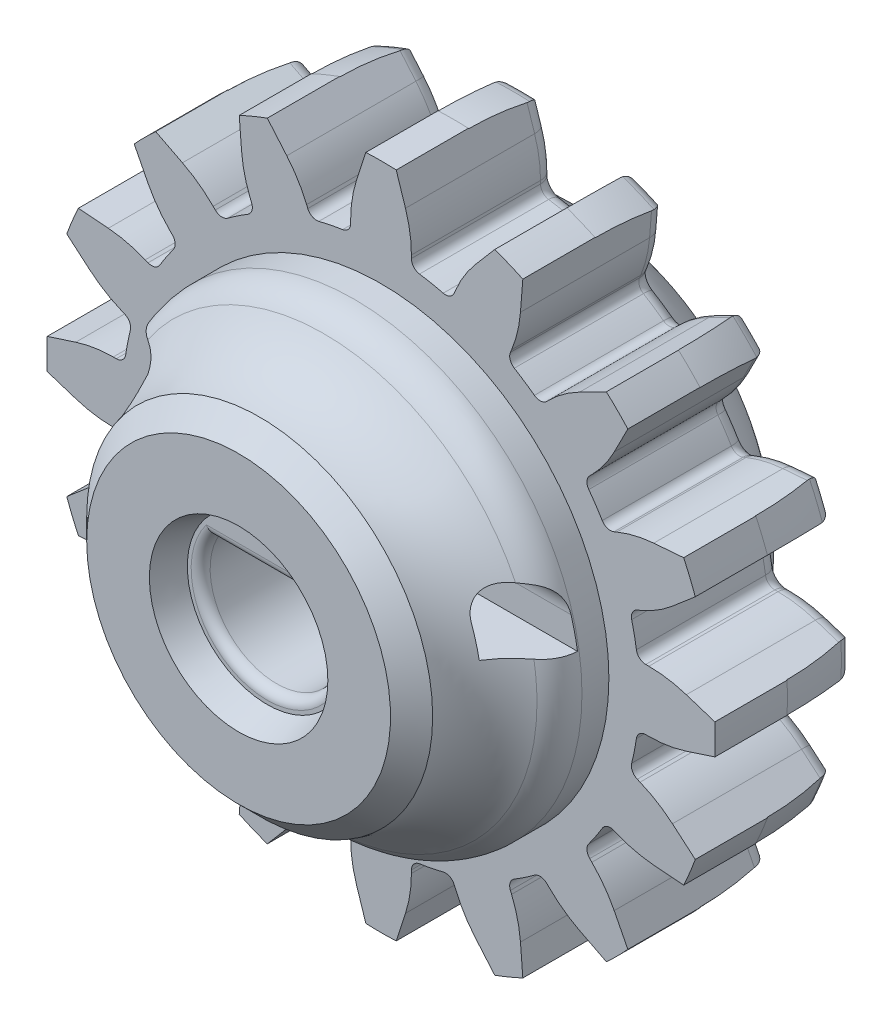
SolidWorks part; units mm, degrees
ref_plane "Front Plane" through (0, 0, 0) normal (0, 0, 1) x (1, 0, 0)
ref_plane "Top Plane" through (0, 0, 0) normal (0, 1, 0) x (1, 0, 0)
ref_plane "Right Plane" through (0, 0, 0) normal (1, 0, 0) x (0, 0, -1)
ref_axis "Axis1" through (0, 0, -12.1515) along (0, 0, 1)
sketch "Sketch1" plane through (0, 0, 0) normal (0, 0, 1) x (1, 0, 0)
  line L0 (0, 0) -> (6.8, 0)
  line L1 (0, 0) -> (0, 6.8) construction
  line L17 (0, 0) -> (0, 6.8)
  arc A0 (6.8, 0) -> (0, 6.8) centre (0, 0) ccw
  dimension "D1" = 13.6
sketch "Sketch4" plane through (0, 0, 0) normal (0, 0, 1) x (1, 0, 0)
  line L0 (0, 0) -> (0, 8.8) construction
  line L1 (-0.4, 8.7909) -> (-0.8, 7.5578)
  line L2 (-0.8, 7.5578) -> (-0.8, 6.7528)
  line L3 (0.8, 7.5578) -> (0.8, 6.7528)
  line L4 (0.4, 8.7909) -> (0.8, 7.5578)
  arc A0 (0.4, 8.7909) -> (-0.4, 8.7909) centre (0, 0) ccw
  arc A2 (0.8, 6.7528) -> (-0.8, 6.7528) centre (0, 0) ccw
  circle A3 centre (0, 0) radius 7.6 construction
  dimension "D1" = 0.4
  dimension "D3" = 15.2
  dimension "D4" = 17.6
  dimension "D2" = 0.8
sketch "Sketch5" plane through (0, 0, 0) normal (1, 0, 0) x (0, 0, -1)
  line L0 (-3, 0) -> (0, 0)
  line L1 (-3.75, 2.1) -> (-3.75, 4.5)
  line L2 (0, 6) -> (3.1175, 6) construction
  line L3 (-2, 0) -> (-2, 5.105) construction
  line L4 (-1.25, 0) -> (-1.25, 6) construction
  line L5 (0, 0) -> (0, 6)
  line L6 (-3.75, 4.5) -> (-6.015, 4.5) construction
  line L7 (0, 6) -> (-1.25, 6)
  line L8 (-3, 0) -> (-3, 2.1)
  line L9 (-3, 2.1) -> (-3.75, 2.1)
  arc A0 (-3.75, 4.5) -> (-1.25, 6) centre (-3.75, 7.3333) ccw
  dimension "D1" = 0.75
  dimension "D2" = 4.5
  dimension "D3" = 1.75
  dimension "D4" = 2
  dimension "D5" = 6
  dimension "D6" = 2.5
  dimension "D7" = 2.1
sketch "Sketch6" plane through (0, 0, 0) normal (0, 0, 1) x (1, 0, 0)
  line L0 (1.4422, 0.9) -> (-1.4422, 0.9) construction
  line L1 (0, 0.9) -> (0, -1.7) construction
  line L2 (1.4697, 0.95) -> (-1.4697, 0.95)
  arc A1 (-1.4422, 0.9) -> (1.4422, 0.9) centre (0, 0) ccw construction
  arc A2 (-1.4697, 0.95) -> (1.4697, 0.95) centre (0, 0) ccw
  dimension "D1" = 1.7
  dimension "D2" = 2.6
  dimension "D3" = 0.05
sketch "Sketch7" plane through (0, 0, 0) normal (1, 0, 0) x (0, 0, -1)
  line L0 (-6.4219, 0.95) -> (11.2671, 0.95) construction
  line L3 (-0.75, 1.7) -> (-0.75, 0.95)
  line L4 (-0.75, 0.95) -> (-2.25, 0.95)
  line L5 (-2.25, 0.95) -> (-2.25, 1.7)
  arc A0 (-0.75, 1.7) -> (-2.25, 1.7) centre (-1.5, 1.7) ccw
  circle A1 centre (-1.5, 1.7) radius 1.4 construction
  dimension "D1" = 1.5
  dimension "D3" = 2.8
extrude "Boss-Extrude1" add sketch "Sketch1" against normal blind 3.8
mirror "Mirror1" about plane through (0, 0, 0) normal (0, 1, 0) of bodies 102
mirror "Mirror2" about plane through (0, 0, 0) normal (1, 0, 0) of bodies 104
extrude "Boss-Extrude2" add sketch "Sketch4" against normal blind 3.8
fillet "Fillet1" radius 3.2 2 edges at (-0.8, 7.5578, -1.9) (0.8, 7.5578, -1.9)
fillet "Fillet2" radius 0.25 2 edges at (0.8, 6.7528, -1.9) (-0.8, 6.7528, -1.9)
pattern_circular "CirPattern1" count 16 over 360 about axis through (0, 0, -12.1515) along (0, 0, 1) of "Fillet1", "Boss-Extrude2", "Fillet2"
sketch "Sketch3" plane through (0, 0, 0) normal (0, 0, 1) x (1, 0, 0)
  line L0 (1.375, 3.1505) -> (3.1505, 1.375)
  line L1 (3.1505, 1.375) -> (5.4544, 1.375)
  line L3 (1.375, 5.4544) -> (1.375, 3.1505)
  arc A0 (1.375, 5.4544) -> (5.4544, 1.375) centre (0, 0) cw
  dimension "D1" = 5.625
revolve "Revolve1" add sketch "Sketch5" angle 360 about axis through (0, 0, -12.1515) along (0, 0, 1) reverse direction yes
sketch "Sketch11" plane through (0, 0, 0) normal (1, 0, 0) x (0, 0, -1)
  line L0 (0, 0) -> (6.05, 0)
  line L1 (12.1515, 0) -> (-7.3064, 0) construction
  line L2 (6.05, 0) -> (6.05, 3)
  line L3 (3.8, 6) -> (3.8, 0) construction
  line L4 (3.8, 6) -> (0, 0)
  line L5 (3.8, 5.9333) -> (3.8, 6.499) construction
  line L6 (3.8, 4.4207) -> (3.8, 5.2292) construction
  arc A0 (3.8, 6) -> (6.05, 3) centre (2.925, 3) cw
  dimension "D1" = 3
  dimension "D2" = 2.25
  dimension "D3" = 6
revolve "Revolve2" add sketch "Sketch11" angle 360 about axis through (0, 0, -12.1515) along (0, 0, 1)
fillet "Fillet3" radius 1 1 edges at (6, 0, 1.25)
extrude "Cut-Extrude1" cut sketch "Sketch6" against normal through all both and the other way through all
fillet "Fillet4" radius 0.25 2 edges at (0, -1.75, 3) (0, 0.95, 3)
extrude "Cut-Extrude2" cut sketch "Sketch7" against normal through all both and the other way through all
sketch "Sketch9" plane through (0, 0, 0) normal (1, 0, 0) x (0, 0, -1)
  circle A0 centre (-1.5, 1.7) radius 0.75 construction
  circle A2 centre (-1.5, 1.7) radius 1.45
  dimension "D1" = 2.9
extrude "Cut-Extrude3" cut sketch "Sketch9" against normal through all from offset 4 offset against normal yes
sketch "Sketch12" plane through (0, 0, 0) normal (1, 0, 0) x (0, 0, -1)
  line L0 (3.8, 8.7909) -> (0, 8.7909) construction
  line L1 (1.9, 8.7909) -> (1.9, 11.1399)
  line L2 (1.9, 11.1399) -> (10.6909, 11.1399)
  line L3 (10.6909, 11.1399) -> (10.6909, 3.6716)
  line L4 (12.1515, 0) -> (-7.3064, 0) construction
  line L5 (9.8576, 3.7359) -> (10.6909, 3.6716)
  arc A0 (1.9, 8.7909) -> (9.8576, 3.7359) centre (1.9, 0) cw
revolve "Cut-Revolve1" cut sketch "Sketch12" angle 360 about axis through (0, 0, -12.1515) along (0, 0, 1)
chamfer "Chamfer2" distance 0.25 distance2 0.75 1 edges at (2.1, 0, 3.75) first distance on face at (2.1, 0, 3.75)
chamfer "Chamfer3" distance 0.5 angle 45 1 edges at (4.5, 0, 3.75)
fillet "Fillet5" radius 0.4 161 edges at (7.2679, -2.187, -3.8) (6.784, -1.9441, -3.8) (6.6193, -1.8104, -3.8) (6.6693, -1.3266, -3.8) (6.8083, -0.8605, -3.8) (7.0116, -0.8, -3.8) (7.5516, -0.7607, -3.8) (8.3046, -0.5577, -3.8) (8.5831, 0, -3.8) (8.3046, 0.5577, -3.8) (7.5516, 0.7607, -3.8) (7.0116, 0.8, -3.8) (6.8083, 0.8605, -3.8) (6.6693, 1.3266, -3.8) (6.6193, 1.8104, -3.8) (6.784, 1.9441, -3.8) (7.2679, 2.187, -3.8) (7.8859, 2.6628, -3.8) (7.9298, 3.2846, -3.8) (7.459, 3.6933, -3.8) (6.6856, 3.5927, -3.8) (6.1717, 3.4223, -3.8) (5.9607, 3.4004, -3.8) (5.654, 3.7779, -3.8) (5.4227, 4.2057, -3.8) (5.5236, 4.3922, -3.8) (5.8777, 4.8019, -3.8) (6.2666, 5.4779, -3.8) (6.0692, 6.0692, -3.8) (5.4779, 6.2666, -3.8) (4.8019, 5.8777, -3.8) (4.3922, 5.5236, -3.8) (4.2057, 5.4227, -3.8) (3.7779, 5.654, -3.8) (3.4004, 5.9607, -3.8) (3.4223, 6.1717, -3.8) (3.5927, 6.6856, -3.8) (3.6933, 7.459, -3.8) (3.2846, 7.9298, -3.8) (2.6628, 7.8859, -3.8) (2.187, 7.2679, -3.8) (1.9441, 6.784, -3.8) (1.8104, 6.6193, -3.8) (1.3266, 6.6693, -3.8) (0.8605, 6.8083, -3.8) (0.8, 7.0116, -3.8) (0.7607, 7.5516, -3.8) (0.5577, 8.3046, -3.8) (0, 8.5831, -3.8) (-0.5577, 8.3046, -3.8) (-0.7607, 7.5516, -3.8) (-0.8, 7.0116, -3.8) (-0.8605, 6.8083, -3.8) (-1.3266, 6.6693, -3.8) (-1.8104, 6.6193, -3.8) (-1.9441, 6.784, -3.8) (-2.187, 7.2679, -3.8) (-2.6628, 7.8859, -3.8) (-3.2846, 7.9298, -3.8) (-3.6933, 7.459, -3.8) (-3.5927, 6.6856, -3.8) (-3.4223, 6.1717, -3.8) (-3.4004, 5.9607, -3.8) (-3.7779, 5.654, -3.8) (-4.2057, 5.4227, -3.8) (-4.3922, 5.5236, -3.8) (-4.8019, 5.8777, -3.8) (-5.4779, 6.2666, -3.8) (-6.0692, 6.0692, -3.8) (-6.2666, 5.4779, -3.8) (-5.8777, 4.8019, -3.8) (-5.5236, 4.3922, -3.8) (-5.4227, 4.2057, -3.8) (-5.654, 3.7779, -3.8) (-5.9607, 3.4004, -3.8) (-6.1717, 3.4223, -3.8) (-6.6856, 3.5927, -3.8) (-7.459, 3.6933, -3.8) (-7.9298, 3.2846, -3.8) (-7.8859, 2.6628, -3.8) (-7.2679, 2.187, -3.8) (-6.784, 1.9441, -3.8) (-6.6193, 1.8104, -3.8) (-6.6693, 1.3266, -3.8) (-6.8083, 0.8605, -3.8) (-7.0116, 0.8, -3.8) (-7.5516, 0.7607, -3.8) (-8.3046, 0.5577, -3.8) (-8.5831, 0, -3.8) (-8.3046, -0.5577, -3.8) (-7.5516, -0.7607, -3.8) (-7.0116, -0.8, -3.8) (-6.8083, -0.8605, -3.8) (-6.6693, -1.3266, -3.8) (-6.6193, -1.8104, -3.8) (-6.784, -1.9441, -3.8) (-7.2679, -2.187, -3.8) (-7.8859, -2.6628, -3.8) (-7.9298, -3.2846, -3.8) (-7.459, -3.6933, -3.8) (-6.6856, -3.5927, -3.8) (-6.1717, -3.4223, -3.8) (-5.9607, -3.4004, -3.8) (-5.654, -3.7779, -3.8) (-5.4227, -4.2057, -3.8) (-5.5236, -4.3922, -3.8) (-5.8777, -4.8019, -3.8) (-6.2666, -5.4779, -3.8) (-6.0692, -6.0692, -3.8) (-5.4779, -6.2666, -3.8) (-4.8019, -5.8777, -3.8) (-4.3922, -5.5236, -3.8) (-4.2057, -5.4227, -3.8) (-3.7779, -5.654, -3.8) (-3.4004, -5.9607, -3.8) (-3.4223, -6.1717, -3.8) (-3.5927, -6.6856, -3.8) (-3.6933, -7.459, -3.8) (-3.2846, -7.9298, -3.8) (-2.6628, -7.8859, -3.8) (-2.187, -7.2679, -3.8) (-1.9441, -6.784, -3.8) (-1.8104, -6.6193, -3.8) (-1.3266, -6.6693, -3.8) (-0.8605, -6.8083, -3.8) (-0.8, -7.0116, -3.8) (-0.7607, -7.5516, -3.8) (-0.5577, -8.3046, -3.8) (0, -8.5831, -3.8) (0.5577, -8.3046, -3.8) (0.7607, -7.5516, -3.8) (0.8, -7.0116, -3.8) (0.8605, -6.8083, -3.8) (1.3266, -6.6693, -3.8) (1.8104, -6.6193, -3.8) (1.9441, -6.784, -3.8) (2.187, -7.2679, -3.8) (2.6628, -7.8859, -3.8) (3.2846, -7.9298, -3.8) (3.6933, -7.459, -3.8) (3.5927, -6.6856, -3.8) (3.4223, -6.1717, -3.8) (3.4004, -5.9607, -3.8) (3.7779, -5.654, -3.8) (4.2057, -5.4227, -3.8) (4.3922, -5.5236, -3.8) (4.8019, -5.8777, -3.8) (5.4779, -6.2666, -3.8) (6.0692, -6.0692, -3.8) (6.2666, -5.4779, -3.8) (5.8777, -4.8019, -3.8) (5.5236, -4.3922, -3.8) (5.4227, -4.2057, -3.8) (5.654, -3.7779, -3.8) (5.9607, -3.4004, -3.8) (6.1717, -3.4223, -3.8) (6.6856, -3.5927, -3.8) (7.459, -3.6933, -3.8) (7.9298, -3.2846, -3.8) (7.8859, -2.6628, -3.8) (-6, 0, -3.8)
